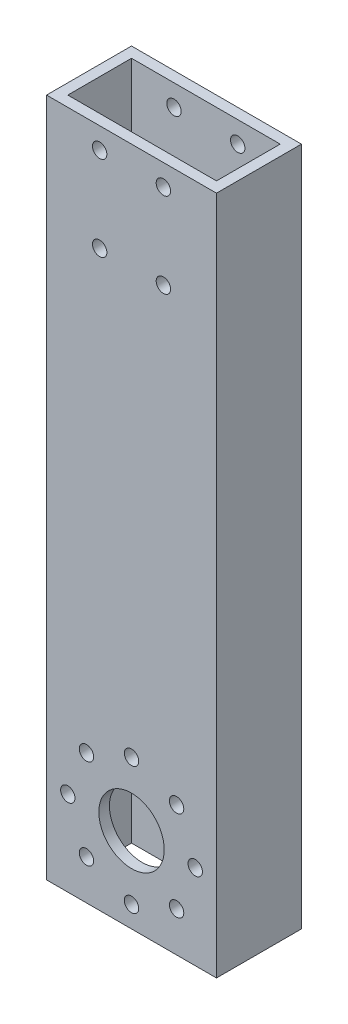
SolidWorks part; units mm, degrees
material "6061-T6 (SS)"
ref_plane "Front Plane" through (0, 0, 0) normal (0, 0, 1) x (1, 0, 0)
ref_plane "Top Plane" through (0, 0, 0) normal (0, 1, 0) x (1, 0, 0)
ref_plane "Right Plane" through (0, 0, 0) normal (1, 0, 0) x (0, 0, -1)
sketch "Sketch2" plane through (0, 0, 0) normal (0, 1, 0) x (1, 0, 0)
  line L1 (-15.1862, -12.028) -> (35.6138, -12.028)
  line L2 (-15.1862, -12.028) -> (-15.1862, 13.372)
  line L3 (-15.1862, 13.372) -> (35.6138, 13.372)
  line L4 (35.6138, -12.028) -> (35.6138, 13.372)
  dimension "D1" = 25.4
  dimension "D2" = 50.8
extrude "Extrude-Thin1" add sketch "Sketch2" along normal blind 457.2 thin thin type one direction reverse wall 3.175
ref_plane "Plane1" through (0, 235.286, -235.286) normal (0, 0.7071, -0.7071) x (-1, 0, 0)
sketch "Sketch8" plane through (0, 235.286, -235.286) normal (0, 0.7071, -0.7071) x (-1, 0, 0)
  line L0 (-35.6138, 313.8338) -> (15.1862, 313.8338) construction
  circle A0 centre (-10.2138, 288.4338) radius 6.35
  point P0 (-10.2138, 288.4338)
  point P3 (-10.2138, 313.8338)
  dimension "D2" = 12.7
  dimension "D1" = 25.4
extrude "Cut-Extrude1" [suppressed] cut sketch "Sketch8" against normal up to surface (63.9513 mm away)
sketch "Sketch9" plane through (-15.1862, 0, 0) normal (-1, 0, 0) x (0, 0, 1)
  line L0 (-13.372, 457.2) -> (12.028, 457.2) construction
  line L1 (-13.372, 457.2) -> (-13.372, 0) construction
  line L2 (2.503, 457.2) -> (-0.672, 520.7) construction
  line L4 (-16.547, 457.2) -> (-3.847, 457.2)
  line L6 (2.503, 457.2) -> (21.553, 457.2)
  line L7 (2.503, 457.2) -> (-3.847, 457.2)
  arc A4 (21.553, 457.2) -> (-16.547, 457.2) centre (2.503, 457.2) ccw
  dimension "D1" = 0
  dimension "D2" = 15.875
extrude "Boss-Extrude5" [suppressed] add sketch "Sketch9" against normal up to surface (3.175 mm away)
sketch "Sketch10" plane through (35.6138, 0, 0) normal (1, 0, 0) x (0, 0, -1)
  line L0 (-12.028, 508) -> (13.372, 508)
  line L12 (13.372, 508) -> (16.547, 508)
  line L13 (-15.203, 508) -> (-12.028, 508)
  arc A2 (16.547, 508) -> (-15.203, 508) centre (0.672, 508) ccw
extrude "Boss-Extrude6" [suppressed] add sketch "Sketch10" against normal up to surface (3.175 mm away)
sketch "Sketch11" [suppressed] plane through (-18.3612, 0, 0) normal (-1, 0, 0) x (0, 0, 1)
  circle A0 centre (-0.672, 508) radius 3.175
  arc A1 (15.203, 508) -> (-16.547, 508) centre (-0.672, 508) ccw construction
  point P6 (-0.672, 523.875)
  dimension "D1" = 6.35
extrude "Cut-Extrude2" [suppressed] cut sketch "Sketch11" against normal up to surface (82.55 mm away)
sketch "Sketch13" plane through (0, 0, 12.028) normal (0, 0, 1) x (1, 0, 0)
  line L0 (-15.1862, 457.2) -> (35.6138, 457.2) construction
  line L1 (-15.1862, 457.2) -> (35.6138, 457.2) construction
  line L3 (35.6138, 457.2) -> (-15.1862, 457.2)
  arc A0 (26.0888, 457.2) -> (-5.6612, 457.2) centre (10.2138, 457.2) ccw construction
  arc A1 (35.6138, 457.2) -> (-15.1862, 457.2) centre (10.2138, 444.8175) ccw
  point P2 (10.2138, 457.2)
  point P7 (35.6138, 457.2)
  point P8 (-15.1862, 457.2)
  point P9 (10.2138, 473.075)
  dimension "D1" = 50.8
  dimension "D2" = 15.875
sketch "Sketch14" plane through (0, 457.2, 0) normal (0, 1, 0) x (1, 0, 0)
  line L1 (32.4388, -8.853) -> (-12.0112, -8.853)
  line L2 (32.4388, -8.853) -> (32.4388, 10.197)
  line L3 (32.4388, 10.197) -> (-12.0112, 10.197)
  line L4 (-12.0112, -8.853) -> (-12.0112, 10.197)
extrude "Extrude-Thin2" [suppressed] add sketch "Sketch14" along normal blind 152.4 thin thin type one direction wall 3.175
sketch "Sketch15" plane through (0, 0, 12.028) normal (0, 0, 1) x (1, 0, 0)
  line L2 (-5.6612, 609.6) -> (26.0888, 609.6)
  line L3 (35.6138, 457.2) -> (-15.1862, 457.2) construction
  arc A1 (26.0888, 609.6) -> (-5.6612, 609.6) centre (10.2138, 609.6) ccw
  dimension "D1" = 31.75
  dimension "D2" = 152.4
extrude "Boss-Extrude7" [suppressed] add sketch "Sketch15" along normal blind 3.175 from offset 22.225
sketch "Sketch17" [suppressed] plane through (0, 0, 15.203) normal (0, 0, 1) x (1, 0, 0)
  line L0 (38.7888, 660.4) -> (38.7888, 584.2)
  line L1 (38.7888, 584.2) -> (38.7888, 508) construction
  line L2 (7.0388, 660.4) -> (7.0388, 584.2)
  line L3 (64.1888, 508) -> (64.1888, 660.4)
  line L4 (64.1888, 660.4) -> (38.7888, 660.4)
  line L5 (-18.3612, 508) -> (-18.3612, 660.4)
  line L6 (-18.3612, 660.4) -> (7.0388, 660.4)
  arc A0 (38.7888, 584.2) -> (64.1888, 508) centre (165.7888, 584.2) ccw
  arc A1 (7.0388, 584.2) -> (-18.3612, 508) centre (-119.9612, 584.2) cw
  dimension "D1" = 76.2
sketch "Sketch18" [suppressed] plane through (0, 0, 40.603) normal (0, 0, 1) x (1, 0, 0)
  line L0 (64.1888, 508) -> (-18.3612, 508) construction
  line L1 (64.1888, 508) -> (-18.3612, 508) construction
  line L2 (38.7888, 660.4) -> (64.1888, 508)
  line L3 (7.0388, 660.4) -> (38.7888, 660.4) construction
  line L4 (7.0388, 660.4) -> (-18.3612, 508)
  line L5 (7.0388, 660.4) -> (38.7888, 660.4)
  line L6 (64.1888, 508) -> (64.1888, 482.6)
  line L7 (64.1888, 482.6) -> (-18.3612, 482.6)
  line L8 (-18.3612, 482.6) -> (-18.3612, 508)
  arc A0 (38.7888, 660.4) -> (7.0388, 660.4) centre (22.9138, 660.4) ccw construction
  dimension "D1" = 25.4
extrude "Boss-Extrude9" [suppressed] add sketch "Sketch18" against normal blind 3.175
sketch "Sketch19" [suppressed] plane through (0, 0, 37.428) normal (0, 0, -1) x (-1, 0, 0)
  line L0 (-64.1888, 508) -> (18.3612, 508)
  line L1 (-64.1888, 508) -> (-64.1888, 482.6)
  line L2 (18.3612, 508) -> (18.3612, 482.6)
  line L3 (-64.1888, 482.6) -> (18.3612, 482.6)
  line L4 (15.1862, 508) -> (-61.0138, 508) construction
  dimension "D1" = 25.4
  dimension "D2" = 82.55
extrude "Boss-Extrude10" [suppressed] add sketch "Sketch19" along normal up to next
sketch "Sketch21" [suppressed] plane through (0, 0, -16.547) normal (0, 0, -1) x (-1, 0, 0)
  line L5 (18.3612, 508) -> (-7.0388, 660.4)
  line L6 (18.3612, 482.6) -> (18.3612, 508)
  line L7 (-64.1888, 482.6) -> (18.3612, 482.6)
  line L8 (-64.1888, 508) -> (-64.1888, 482.6)
  line L9 (-38.7888, 660.4) -> (-64.1888, 508)
  line L10 (18.3612, 508) -> (-7.0388, 660.4)
  line L11 (18.3612, 482.6) -> (18.3612, 508)
  line L12 (-64.1888, 482.6) -> (18.3612, 482.6)
  line L13 (-64.1888, 508) -> (-64.1888, 482.6)
  line L14 (-38.7888, 660.4) -> (-64.1888, 508)
  arc A1 (-7.0388, 660.4) -> (-38.7888, 660.4) centre (-22.9138, 660.4) ccw
  arc A2 (-7.0388, 660.4) -> (-38.7888, 660.4) centre (-22.9138, 660.4) ccw
  dimension "D1" = 0
extrude "Boss-Extrude12" [suppressed] add sketch "Sketch21" along normal blind 3.175 from offset 22.225 separate body
sketch "Sketch22" [suppressed] plane through (0, 0, -38.772) normal (0, 0, 1) x (1, 0, 0)
  line L1 (64.1888, 482.6) -> (-18.3612, 482.6)
  line L2 (64.1888, 482.6) -> (64.1888, 508)
  line L3 (64.1888, 508) -> (-18.3612, 508)
  line L4 (-18.3612, 482.6) -> (-18.3612, 508)
extrude "Boss-Extrude13" [suppressed] add sketch "Sketch22" along normal up to surface (22.225 mm away)
sketch "Sketch16" [suppressed] plane through (0, 0, 15.203) normal (0, 0, 1) x (1, 0, 0)
  arc A0 (38.7888, 660.4) -> (7.0388, 660.4) centre (22.9138, 660.4) ccw construction
  arc A1 (38.7888, 660.4) -> (7.0388, 660.4) centre (22.9138, 660.4) ccw construction
  circle A2 centre (22.9138, 660.4) radius 3.175
  dimension "D1" = 6.35
extrude "Cut-Extrude6" [suppressed] cut sketch "Sketch16" against normal through all both and the other way through all
sketch "Sketch23" plane through (0, 457.2, 0) normal (0, 1, 0) x (1, 0, 0)
  line L1 (91.5301, -40.8812) -> (-34.4515, -40.8812)
  line L2 (91.5301, -40.8812) -> (91.5301, 37.0604)
  line L3 (91.5301, 37.0604) -> (-34.4515, 37.0604)
  line L4 (-34.4515, -40.8812) -> (-34.4515, 37.0604)
sketch "Sketch25" plane through (0, 0, 0) normal (0, -1, 0) x (1, 0, 0)
  line L0 (-12.0112, -10.197) -> (-12.0112, 8.853) construction
  line L1 (32.4388, -10.197) -> (-12.0112, -10.197) construction
  line L2 (-12.0112, 8.853) -> (32.4388, 8.853) construction
  line L3 (32.4388, 8.853) -> (32.4388, -10.197) construction
  line L4 (-15.1862, 12.028) -> (-15.1862, -13.372)
  line L5 (-15.1862, -13.372) -> (35.6138, -13.372)
  line L6 (35.6138, -13.372) -> (35.6138, 12.028)
  line L7 (35.6138, 12.028) -> (-15.1862, 12.028)
  line L8 (-15.1862, 12.028) -> (-15.1862, -13.372)
  line L9 (-15.1862, -13.372) -> (35.6138, -13.372)
  line L10 (35.6138, -13.372) -> (35.6138, 12.028)
  line L11 (35.6138, 12.028) -> (-15.1862, 12.028)
  line L12 (-12.0112, -10.197) -> (-12.0112, 8.853)
  line L13 (32.4388, -10.197) -> (-12.0112, -10.197)
  line L14 (-12.0112, 8.853) -> (32.4388, 8.853)
  line L15 (32.4388, 8.853) -> (32.4388, -10.197)
  dimension "D1" = 0
extrude "Boss-Extrude14" add sketch "Sketch25" along normal blind 25.4
sketch "Sketch28" plane through (0, 0, -13.372) normal (0, 0, -1) x (-1, 0, 0)
  line L0 (9.8842, -20.0979) -> (-30.3117, 20.0979) construction
  line L1 (-35.6138, 457.2) -> (-35.6138, -25.4) construction
  line L2 (15.1862, -25.4) -> (-35.6138, -25.4) construction
  line L3 (9.285, 19.4988) -> (-29.7126, -19.4988) construction
  line L4 (-10.2138, 0) -> (-10.2138, 61.5696) construction
  circle A0 centre (-10.2138, 0) radius 12.954
  circle A1 centre (-10.2138, 0) radius 19.05 construction
  circle A2 centre (-23.6841, -13.4704) radius 2.1527
  circle A3 centre (-29.2638, 0) radius 2.1527
  circle A4 centre (-23.6841, 13.4704) radius 2.1527
  circle A5 centre (-10.2138, 19.05) radius 2.1526
  circle A6 centre (3.2566, 13.4704) radius 2.1526
  circle A7 centre (8.8362, 0) radius 2.1526
  circle A8 centre (3.2566, -13.4704) radius 2.1526
  circle A9 centre (-10.2138, -19.05) radius 2.1526
  point P7 (-29.2638, 0)
  point P8 (-10.2138, 19.05)
  point P9 (8.8362, 0)
  point P10 (-10.2138, -19.05)
  point P11 (3.2566, -13.4704)
  point P15 (-10.2138, 0)
  point P17 (-10.2138, 0)
  point P19 (-23.6841, -13.4704)
  point P20 (-23.6841, 13.4704)
  point P21 (3.2566, 13.4704)
  dimension "D1" = 25.908
  dimension "D3" = 25.4
  dimension "D4" = 38.1
  dimension "D7" = 4.3053
  dimension "D2" = 25.4
  dimension "D5" = 45
  dimension "D6" = 45
extrude "Cut-Extrude9" [suppressed] cut sketch "Sketch28" against normal up to surface (25.4 mm away)
sketch "Sketch29" plane through (0, 457.2, 0) normal (0, 1, 0) x (1, 0, 0)
  line L0 (-12.0112, 10.197) -> (-12.0112, -8.853) construction
  line L1 (-12.0112, -8.853) -> (32.4388, -8.853) construction
  line L2 (32.4388, 10.197) -> (-12.0112, 10.197) construction
  line L3 (32.4388, -8.853) -> (32.4388, 10.197) construction
  line L4 (-15.1862, 13.372) -> (-15.1862, -12.028)
  line L5 (-15.1862, -12.028) -> (35.6138, -12.028)
  line L6 (35.6138, -12.028) -> (35.6138, 13.372)
  line L7 (35.6138, 13.372) -> (-15.1862, 13.372)
  line L8 (-15.1862, 13.372) -> (-15.1862, -12.028)
  line L9 (-15.1862, -12.028) -> (35.6138, -12.028)
  line L10 (35.6138, -12.028) -> (35.6138, 13.372)
  line L11 (35.6138, 13.372) -> (-15.1862, 13.372)
  line L12 (-12.0112, 10.197) -> (-12.0112, -8.853)
  line L13 (-12.0112, -8.853) -> (32.4388, -8.853)
  line L14 (32.4388, 10.197) -> (-12.0112, 10.197)
  line L15 (32.4388, -8.853) -> (32.4388, 10.197)
  dimension "D1" = 0
extrude "Cut-Extrude10" cut sketch "Sketch29" against normal blind 203.2
sketch "Sketch30" [suppressed] plane through (0, 457.2, 0) normal (0, 1, 0) x (1, 0, 0)
  line L4 (-15.1862, 13.372) -> (-15.1862, -12.028)
  line L5 (-15.1862, -12.028) -> (35.6138, -12.028)
  line L6 (35.6138, -12.028) -> (35.6138, 13.372)
  line L7 (35.6138, 13.372) -> (-15.1862, 13.372)
  line L10 (35.6138, -12.028) -> (35.6138, 13.372)
  line L12 (-15.1862, 13.372) -> (-15.1862, -12.028)
  line L13 (-15.1862, -12.028) -> (35.6138, -12.028)
  line L14 (35.6138, -12.028) -> (35.6138, 13.372)
  line L15 (35.6138, 13.372) -> (-15.1862, 13.372)
  dimension "D1" = 0
extrude "Cut-Extrude11" [suppressed] cut sketch "Sketch30" against normal blind 44.45
sketch "Sketch32" [suppressed] plane through (0, 457.2, 0) normal (0, 1, 0) x (1, 0, 0)
  line L1 (55.4573, 34.4048) -> (-49.9988, 34.4048)
  line L2 (55.4573, 34.4048) -> (55.4573, -79.0273)
  line L3 (55.4573, -79.0273) -> (-49.9988, -79.0273)
  line L4 (-49.9988, 34.4048) -> (-49.9988, -79.0273)
extrude "Cut-Extrude13" [suppressed] cut sketch "Sketch32" against normal blind 152.4
sketch "Sketch33" [suppressed] plane through (0, 0, -13.372) normal (0, 0, -1) x (-1, 0, 0)
  line L0 (15.1862, 304.8) -> (-35.6138, 304.8) construction
  line L1 (15.1862, 304.8) -> (-35.6138, 304.8) construction
  line L2 (-10.2138, 304.8) -> (-10.2138, 260.9105) construction
  circle A0 centre (-22.9138, 295.275) radius 2.1526
  circle A2 centre (-22.9138, 276.225) radius 2.1526
  circle A5 centre (2.4862, 295.275) radius 2.1526
  circle A6 centre (2.4862, 276.225) radius 2.1526
  dimension "D1" = 4.3053
  dimension "D2" = 9.525
  dimension "D3" = 19.05
  dimension "D4" = 12.7
extrude "Cut-Extrude14" [suppressed] cut sketch "Sketch33" against normal up to surface (25.4 mm away)
sketch "Sketch34" plane through (0, 0, 12.028) normal (0, 0, 1) x (1, 0, 0)
  line L0 (35.6138, -25.4) -> (-15.1862, -25.4) construction
  line L1 (-15.1862, 254) -> (-15.1862, -25.4) construction
  line L2 (10.2138, 0) -> (58.1998, 0) construction
  line L3 (-29.5569, 39.7707) -> (49.9845, -39.7707) construction
  line L4 (-21.4398, -31.6535) -> (41.8673, 31.6535) construction
  line L5 (10.2138, 0) -> (10.2138, -82.8686) construction
  circle A0 centre (10.2138, 0) radius 9.779
  circle A1 centre (10.2138, 0) radius 19.05 construction
  circle A2 centre (29.2638, 0) radius 2.1527
  circle A3 centre (23.6841, 13.4704) radius 2.1527
  circle A4 centre (10.2138, 19.05) radius 2.1526
  circle A5 centre (-3.2566, 13.4704) radius 2.1527
  circle A6 centre (-8.8362, 0) radius 2.1526
  circle A7 centre (-3.2566, -13.4704) radius 2.1526
  circle A8 centre (10.2138, -19.05) radius 2.1526
  circle A9 centre (23.6841, -13.4704) radius 2.1527
  point P7 (10.2138, 19.05)
  point P13 (10.2138, 0)
  point P16 (10.2138, 0)
  point P18 (-8.8362, 0)
  point P19 (10.2138, -19.05)
  point P20 (29.2638, 0)
  point P21 (23.6841, 13.4704)
  point P22 (-3.2566, 13.4704)
  point P23 (10.2138, -19.05)
  point P24 (23.6841, -13.4704)
  dimension "D1" = 19.558
  dimension "D4" = 38.1
  dimension "D7" = 4.3053
  dimension "D2" = 25.4
  dimension "D3" = 25.4
  dimension "D5" = 45
  dimension "D6" = 45
extrude "Cut-Extrude15" cut sketch "Sketch34" against normal up to surface (25.4 mm away) up to face at (10.2138, 114.3, -13.372)
sketch "Sketch35" plane through (0, 254, 0) normal (0, 1, 0) x (1, 0, 0)
  line L1 (35.6138, 13.372) -> (-15.1862, 13.372)
  line L2 (35.6138, 13.372) -> (35.6138, -12.028)
  line L3 (35.6138, -12.028) -> (-15.1862, -12.028)
  line L4 (-15.1862, 13.372) -> (-15.1862, -12.028)
extrude "Cut-Extrude16" cut sketch "Sketch35" against normal blind 76.2
sketch "Sketch31" plane through (0, 0, -13.372) normal (0, 0, -1) x (-1, 0, 0)
  line L1 (-35.6138, 177.8) -> (-35.6138, -25.4) construction
  line L2 (-35.6138, 177.8) -> (15.1862, 177.8) construction
  circle A0 centre (-19.7388, 146.05) radius 2.1527
  circle A1 centre (-0.6888, 146.05) radius 2.1527
  circle A2 centre (-19.7388, 171.45) radius 2.1527
  circle A3 centre (-0.6888, 171.45) radius 2.1527
  dimension "D1" = 4.3053
  dimension "D2" = 6.35
  dimension "D3" = 25.4
  dimension "D4" = 15.875
  dimension "D5" = 19.05
extrude "Cut-Extrude12" cut sketch "Sketch31" against normal through all both and the other way through all
equation "\"0.625n\"=0.5"
